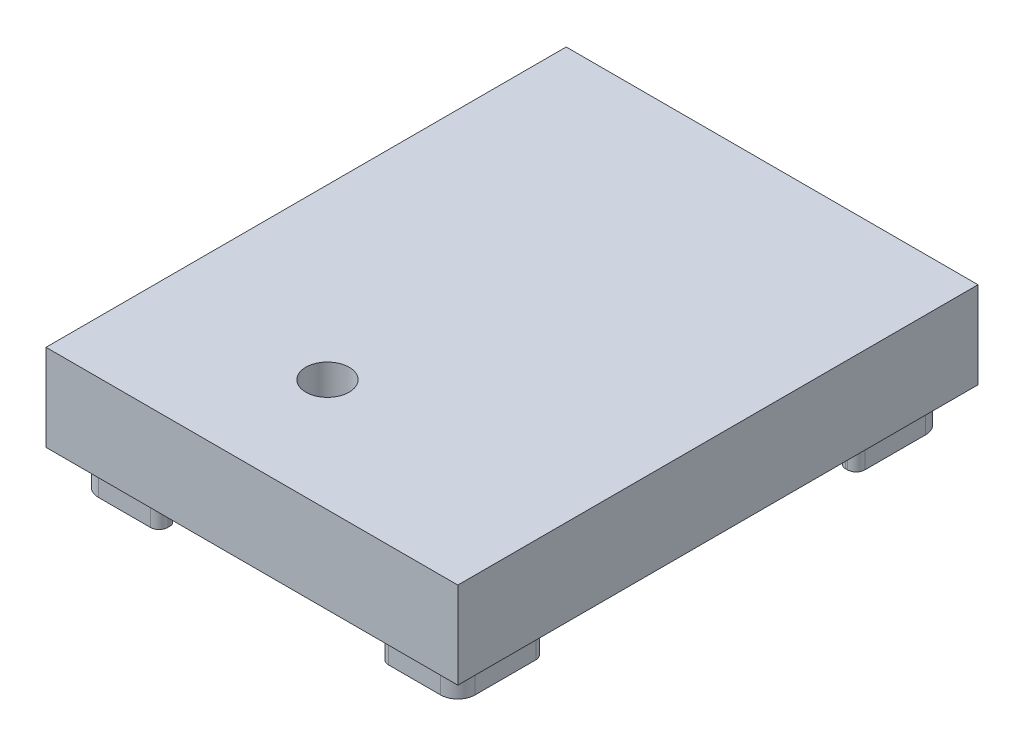
SolidWorks part; units mm, degrees
ref_plane "Front Plane" through (0, 0, 0) normal (0, 0, 1) x (1, 0, 0)
ref_plane "Top Plane" through (0, 0, 0) normal (0, 1, 0) x (1, 0, 0)
ref_plane "Right Plane" through (0, 0, 0) normal (1, 0, 0) x (0, 0, -1)
sketch "Sketch2" plane through (0, 0, 0) normal (0, 1, 0) x (1, 0, 0)
  line L1 (-47.5, -60) -> (47.5, -60)
  line L2 (-47.5, -60) -> (-47.5, 60)
  line L3 (-47.5, 60) -> (47.5, 60)
  line L4 (47.5, -60) -> (47.5, 60)
  line L5 (-47.5, -60) -> (47.5, 60) construction
  line L6 (-47.5, 60) -> (47.5, -60) construction
  point P0 (0, 0)
  dimension "D1" = 120
  dimension "D2" = 95
extrude "top plate" add sketch "Sketch2" along normal blind 20
sketch "Sketch3" plane through (0, 0, 0) normal (0, -1, 0) x (1, 0, 0)
  line L0 (-37.45, 51.95) -> (-26.95, 51.95)
  line L3 (-41.45, 35.95) -> (-40.95, 35.95)
  line L10 (-25.45, 53.95) -> (-25.45, 53.45)
  line L11 (-27.45, 55.95) -> (-39.45, 55.95)
  line L12 (-43.45, 51.95) -> (-43.45, 37.95)
  line L13 (-47.5, 60) -> (47.5, 60) construction
  line L14 (-47.5, -60) -> (-47.5, 60) construction
  line L15 (-39.45, 49.95) -> (-39.45, 37.45)
  arc A0 (-43.45, 51.95) -> (-39.45, 55.95) centre (-39.45, 51.95) cw
  arc A1 (-25.45, 53.95) -> (-27.45, 55.95) centre (-27.45, 53.95) ccw
  arc A2 (-39.45, 49.95) -> (-37.45, 51.95) centre (-37.45, 49.95) cw
  arc A3 (-40.95, 35.95) -> (-39.45, 37.45) centre (-40.95, 37.45) ccw
  arc A4 (-26.95, 51.95) -> (-25.45, 53.45) centre (-26.95, 53.45) ccw
  arc A5 (-43.45, 37.95) -> (-41.45, 35.95) centre (-41.45, 37.95) ccw
  point P12 (-43.45, 55.95)
  point P23 (-43.45, 35.95)
  dimension "D7" = 4
  dimension "D8" = 2
  dimension "D9" = 2
  dimension "D10" = 1.5
  dimension "D11" = 2
  dimension "D1" = 4.05
  dimension "D2" = 20
  dimension "D3" = 4
  dimension "D4" = 4.05
  dimension "D5" = 18
  dimension "D6" = 4
extrude "friction clip" add sketch "Sketch3" along normal blind 8
mirror "4 clips" about plane through (0, 0, 0) normal (0, 0, 1) of "friction clip" second plane through (0, 0, 0) second plane normal (1, 0, 0)
sketch "Sketch8" plane through (0, 0, 0) normal (0, -1, 0) x (1, 0, 0)
  line L1 (-36.8642, -51.3642) -> (36.8642, -51.3642)
  line L2 (-38.8642, -49.3642) -> (-38.8642, 49.3642)
  line L3 (-36.8642, 51.3642) -> (36.8642, 51.3642)
  line L4 (38.8642, -49.3642) -> (38.8642, 49.3642)
  line L5 (-38.8642, -51.3642) -> (38.8642, 51.3642) construction
  line L6 (-38.8642, 51.3642) -> (38.8642, -51.3642) construction
  arc A0 (39.45, 49.95) -> (37.45, 51.95) centre (37.45, 49.95) ccw construction
  arc A1 (36.8642, -51.3642) -> (38.8642, -49.3642) centre (36.8642, -49.3642) ccw
  arc A2 (-36.8642, -51.3642) -> (-38.8642, -49.3642) centre (-36.8642, -49.3642) cw
  arc A3 (-38.8642, 49.3642) -> (-36.8642, 51.3642) centre (-36.8642, 49.3642) cw
  arc A4 (36.8642, 51.3642) -> (38.8642, 49.3642) centre (36.8642, 49.3642) cw
  point P0 (0, 0)
  dimension "D1" = 2
extrude "Cut-Extrude1" cut sketch "Sketch8" against normal blind 15
sketch "Sketch5" plane through (0, 20, 0) normal (0, 1, 0) x (1, 0, 0)
  line L0 (-47.5, -60) -> (47.5, -60) construction
  line L1 (-47.5, 60) -> (-47.5, -60) construction
  circle A0 centre (-8.56, -34.015) radius 5
  dimension "D3" = 10
  dimension "D1" = 25.985
  dimension "D2" = 38.94
extrude "snooze hole" cut sketch "Sketch5" against normal through all
sketch "Sketch6" plane through (0, 0, 0) normal (0, -1, 0) x (1, 0, 0)
  circle A0 centre (-8.56, 34.015) radius 5 construction
  circle A1 centre (-8.56, 34.015) radius 5
  circle A2 centre (-8.56, 34.015) radius 8
  dimension "D1" = 16
extrude "snooze hole support" add sketch "Sketch6" along normal blind 15 and the other way up to surface (15 mm away) other way up to face at (-8.56, 15, 29.015)
